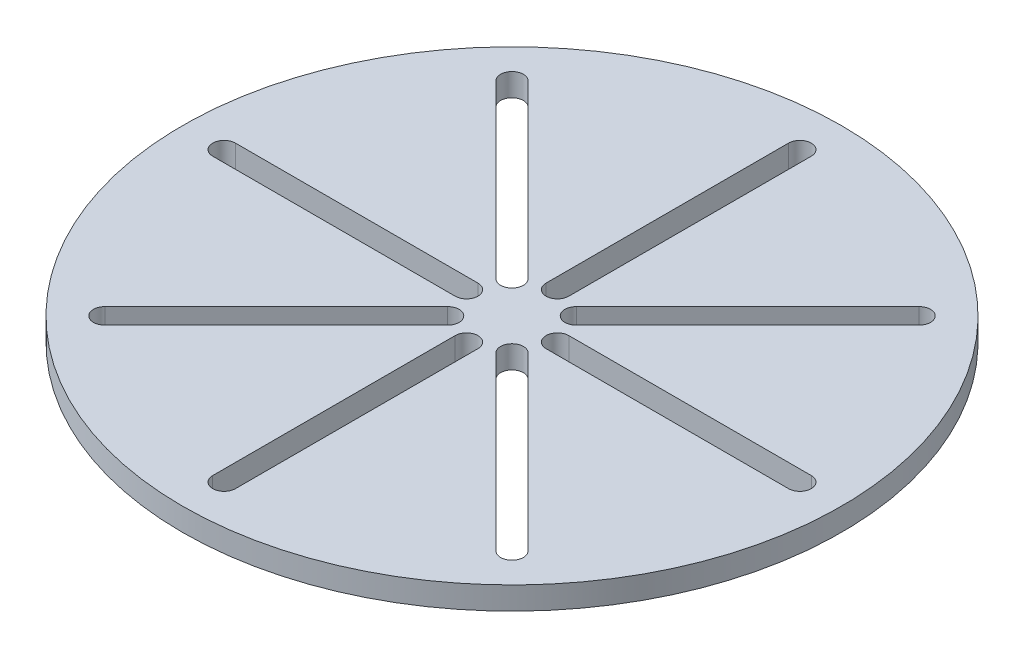
SolidWorks part; units mm, degrees
ref_plane "Front Plane" through (0, 0, 0) normal (0, 0, 1) x (1, 0, 0)
ref_plane "Top Plane" through (0, 0, 0) normal (0, 1, 0) x (1, 0, 0)
ref_plane "Right Plane" through (0, 0, 0) normal (1, 0, 0) x (0, 0, -1)
sketch "Sketch1" plane through (0, 0, 0) normal (0, 1, 0) x (1, 0, 0)
  line L0 (5.08, 5.08) -> (5.08, 55.88) construction
  line L5 (2.6988, 5.08) -> (2.6988, 55.88)
  line L6 (7.4612, 5.08) -> (7.4612, 55.88)
  line L7 (5.08, 5.08) -> (5.08, 4.5959) construction
  line L8 (0, 30.48) -> (10.16, 30.48) construction
  line L9 (5.08, 5.08) -> (5.08, 4.5959) construction
  line L10 (11.8152, 2.2902) -> (47.7362, 38.2112) construction
  line L11 (10.1314, 3.974) -> (46.0524, 39.895)
  line L12 (13.499, 0.6064) -> (49.42, 36.5274)
  line L13 (14.605, -4.445) -> (65.405, -4.445) construction
  line L14 (14.605, -2.0638) -> (65.405, -2.0638)
  line L15 (14.605, -6.8262) -> (65.405, -6.8263)
  line L16 (11.8152, -11.1802) -> (47.7362, -47.1012) construction
  line L17 (13.499, -9.4964) -> (49.42, -45.4174)
  line L18 (10.1314, -12.864) -> (46.0524, -48.785)
  line L19 (5.08, -13.97) -> (5.08, -64.77) construction
  line L22 (7.4613, -13.97) -> (7.4612, -64.77)
  line L25 (5.08, 58.2613) -> (5.08, 64.6112) construction
  line L27 (2.6987, -13.97) -> (2.6987, -64.77)
  line L28 (-1.6552, -11.1802) -> (-37.5762, -47.1012) construction
  line L30 (0.0286, -12.864) -> (-35.8924, -48.785)
  line L31 (-3.339, -9.4964) -> (-39.26, -45.4174)
  line L33 (-4.445, -4.445) -> (-55.245, -4.445) construction
  line L34 (-4.445, -6.8262) -> (-55.245, -6.8262)
  line L37 (-4.445, -2.0638) -> (-55.245, -2.0638)
  line L39 (-1.6552, 2.2902) -> (-37.5762, 38.2112) construction
  line L51 (5.08, 2.6987) -> (5.08, -0.1869) construction
  line L52 (5.08, 2.6987) -> (5.08, -4.445) construction
  line L53 (-3.339, 0.6064) -> (-39.26, 36.5274)
  line L54 (0.0286, 3.974) -> (-35.8924, 39.895)
  arc A0 (2.6988, 5.08) -> (7.4612, 5.08) centre (5.08, 5.08) ccw
  arc A1 (7.4612, 55.88) -> (2.6988, 55.88) centre (5.08, 55.88) ccw
  arc A2 (10.1314, 3.974) -> (13.499, 0.6064) centre (11.8152, 2.2902) ccw
  arc A3 (49.42, 36.5274) -> (46.0524, 39.895) centre (47.7362, 38.2112) ccw
  arc A4 (14.605, -2.0638) -> (14.605, -6.8262) centre (14.605, -4.445) ccw
  arc A5 (65.405, -6.8263) -> (65.405, -2.0638) centre (65.405, -4.445) ccw
  arc A6 (13.499, -9.4964) -> (10.1314, -12.864) centre (11.8152, -11.1802) ccw
  arc A7 (46.0524, -48.785) -> (49.42, -45.4174) centre (47.7362, -47.1012) ccw
  circle A12 centre (5.08, -4.445) radius 69.0563
  arc A13 (7.4613, -13.97) -> (2.6987, -13.97) centre (5.08, -13.97) ccw
  arc A14 (2.6987, -64.77) -> (7.4612, -64.77) centre (5.08, -64.77) ccw
  arc A15 (0.0286, -12.864) -> (-3.339, -9.4964) centre (-1.6552, -11.1802) ccw
  arc A16 (-39.26, -45.4174) -> (-35.8924, -48.785) centre (-37.5762, -47.1012) ccw
  arc A17 (-4.445, -6.8262) -> (-4.445, -2.0638) centre (-4.445, -4.445) ccw
  arc A18 (-55.245, -2.0638) -> (-55.245, -6.8262) centre (-55.245, -4.445) ccw
  arc A19 (-3.339, 0.6064) -> (0.0286, 3.974) centre (-1.6552, 2.2902) ccw
  arc A20 (-35.8924, 39.895) -> (-39.26, 36.5274) centre (-37.5762, 38.2112) ccw
  point P7 (5.08, 30.48)
  point P12 (5.08, -39.37)
  point P18 (5.08, 30.48)
  point P23 (29.7757, 20.2507)
  point P30 (40.005, -4.445)
  point P37 (29.7757, -29.1407)
  point P42 (5.08, -4.445)
  point P48 (-19.6157, -29.1407)
  point P55 (-29.845, -4.445)
  point P62 (-19.6157, 20.2507)
  dimension "D2" = 50.8
  dimension "D1" = 2.3813
  dimension "D5" = 9.525
  dimension "D3" = 6.35
  dimension "D6" = 8
extrude "Boss-Extrude1" add sketch "Sketch1" along normal blind 4.7625
ref_axis "Axis1" through (5.08, 0, 4.445) along (0, 1, 0)
equation "\"slot-radius\"=3/32"
equation "\"slot-end-angle\"=60"
equation "\"slot-spacing-angle\"=60"
equation "\"slot-gap\"=0.01"
equation "\"pulley-thickness\"=0.25"
equation "\"pin-diameter\"=2*\"slot-radius\"-2*\"slot-gap\""
equation "\"D1@Sketch1\"=\"slot-radius\""
equation "\"vert-line-length\"=2.0in"
equation "\"test\"=1"
equation "\"D2@Sketch1\"=\"vert-line-length\""
equation "\"disc-thickness\"=0.1875in"
equation "\"D1@Boss-Extrude1\"=\"disc-thickness\""
equation "\"center-distance\"=0.375in"
equation "\"D5@Sketch1\"=\"center-distance\""
equation "\"slot-to-disc-OD\"=1.0in"
equation "\"number-slots\"=8"
equation "\"D6@Sketch1\"=\"number-slots\""
